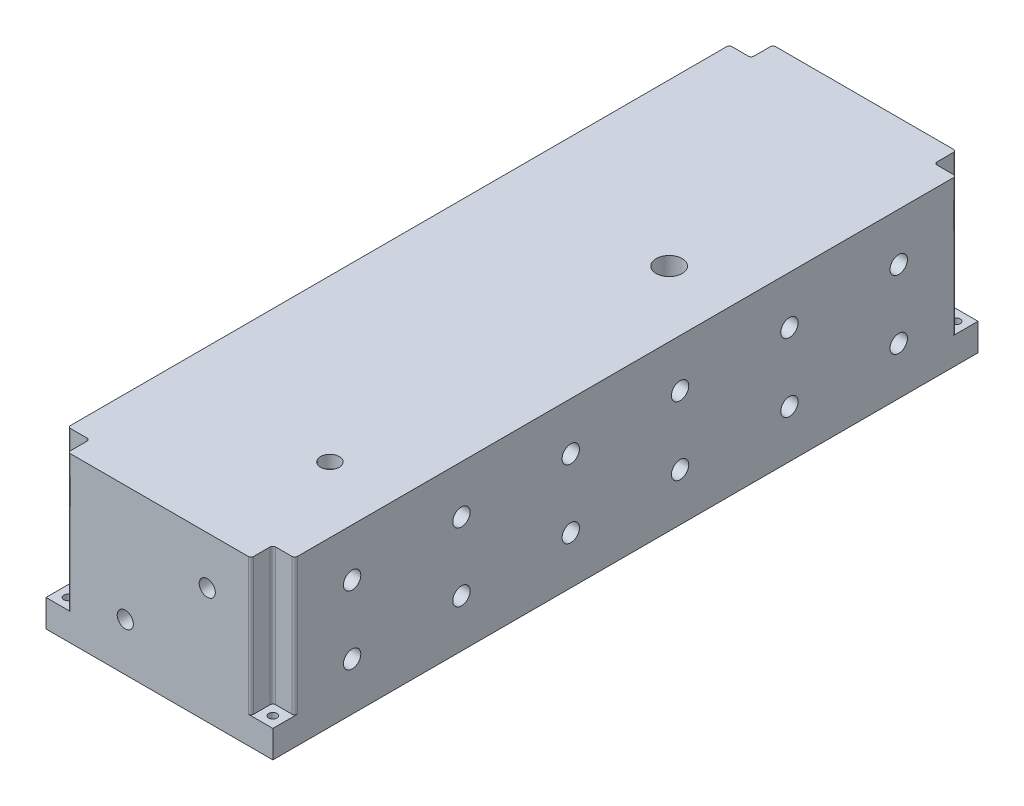
SolidWorks part; units mm, degrees
material "Liga 6061"
ref_plane "Plano frontal" through (0, 0, 0) normal (0, 0, 1) x (1, 0, 0)
ref_plane "Plano superior" through (0, 0, 0) normal (0, 1, 0) x (1, 0, 0)
ref_plane "Plano direito" through (0, 0, 0) normal (1, 0, 0) x (0, 0, -1)
sketch "Esboço1" plane through (0, 0, 0) normal (0, 0, 1) x (1, 0, 0)
  line L0 (83, 0) -> (83, 120) construction
  line L1 (0, 120) -> (166, 120)
  line L2 (0, 120) -> (0, 0)
  line L3 (0, 0) -> (166, 0)
  line L4 (166, 120) -> (166, 0)
  circle A0 centre (118, 85) radius 9.525 construction
  circle A1 centre (58, 35) radius 9.525 construction
  circle A2 centre (118, 85) radius 24 construction
  circle A3 centre (58, 35) radius 24 construction
  dimension "D4" = 19.05
  dimension "D5" = 19.05
  dimension "D6" = 50
  dimension "D7" = 35
  dimension "D8" = 25
  dimension "D3" = 35
  dimension "D1" = 166
  dimension "D2" = 120
extrude "Ressalto-extrusão2" add sketch "Esboço1" along normal blind 516
sketch "Esboço19" plane through (0, 0, 0) normal (0, 0, -1) x (-1, 0, 0)
  circle A1 centre (-118, 85) radius 9.525 construction
  circle A2 centre (-118, 85) radius 9.525
extrude "FuroLinhaP" cut sketch "Esboço19" against normal offset from surface (490.6 mm away) 25.4 up to face at (83, 60, 516)
sketch "Esboço21" plane through (0, 0, 0) normal (0, 0, -1) x (-1, 0, 0)
  circle A1 centre (-58, 35) radius 9.525 construction
  circle A2 centre (-58, 35) radius 9.525
extrude "FuroLinhaT" cut sketch "Esboço21" against normal offset from surface (490.6 mm away) 25.4 up to face at (83, 60, 516)
ref_axis "EixoP" through (118, 85, 490.6) along (0, 0, -1)
ref_axis "EixoT" through (58, 35, 490.6) along (0, 0, -1)
sketch "Esboço3" plane through (0, 0, 0) normal (0, 0, -1) x (-1, 0, 0)
  text T0 "P"
  dimension "D1" = 30.4313
extrude "LetraP" add sketch "Esboço3" along normal blind 0.5
sketch "Esboço4" plane through (0, 0, 0) normal (0, 0, -1) x (-1, 0, 0)
  text T0 "T"
  dimension "D1" = 19.8213
extrude "LetraT" cut sketch "Esboço4" against normal blind 0.5
sketch "Esboço12" plane through (0, 120, 0) normal (0, 1, 0) x (1, 0, 0)
  line L1 (166, 0) -> (150, 0)
  line L2 (166, 0) -> (166, -16)
  line L3 (166, -16) -> (150, -16)
  line L4 (150, 0) -> (150, -16)
  line L5 (0, -258) -> (166, -258) construction
  line L6 (0, -516) -> (0, 0) construction
  line L7 (166, -516) -> (166, 0) construction
  line L10 (166, 0) -> (0, 0) construction
  line L11 (83, -516) -> (83, 0) construction
  line L12 (166, -516) -> (0, -516) construction
  line L13 (16, 0) -> (16, -16)
  line L14 (0, -16) -> (16, -16)
  line L15 (0, 0) -> (0, -16)
  line L16 (0, 0) -> (16, 0)
  line L17 (0, -516) -> (16, -516)
  line L18 (0, -516) -> (0, -500)
  line L19 (0, -500) -> (16, -500)
  line L20 (16, -516) -> (16, -500)
  line L21 (150, -516) -> (150, -500)
  line L22 (166, -500) -> (150, -500)
  line L23 (166, -516) -> (166, -500)
  line L24 (166, -516) -> (150, -516)
  circle A0 centre (120.5, -8) radius 3 construction
  circle A1 centre (120.5, -8) radius 5.775 construction
  dimension "D6" = 6
  dimension "D7" = 11.55
  dimension "D1" = 16
  dimension "D2" = 16
  dimension "D3" = 258
  dimension "D4" = 37.5
  dimension "D5" = 8
extrude "Corte-extrusão5" cut sketch "Esboço12" against normal offset from surface (100 mm away) 20 up to face at (83, 0, 258)
hole_wizard "Furos-guia com Ø6.0mm1" positions "Esboço13" profile "Esboço14" hole size "Ø6.0" standard "ISO" end condition through all
sketch "Esboço13" plane through (0, 20, 0) normal (0, 1, 0) x (1, 0, 0)
  line L1 (166, 0) -> (150, 0) construction
  line L2 (150, 0) -> (16, 0) construction
  point P0 (158, -8)
  point P9 (83, 0)
  dimension "D1" = 75
  dimension "D2" = 8
sketch "Esboço14" plane through (158, 20, 8) normal (1, 0, 0) x (0, 0, 1)
  line L0 (0, 0) -> (0, 20)
  line L1 (0, 20) -> (3, 20)
  line L2 (3, 20) -> (3, 0)
  line L5 (3, 0) -> (0, 0)
  line L11 (0, -6.35) -> (0, 107.95) construction
  dimension "Thru Hole Dia." = 6
  dimension "Thru Hole Depth" = 20
ref_plane "Plano2" through (83, 0, 0) normal (1, 0, 0) x (0, 0, -1)
ref_plane "Plano3" through (0, 0, 258) normal (0, 0, 1) x (1, 0, 0)
mirror "Espelhar1" about plane through (0, 0, 258) normal (0, 0, 1) of "Furos-guia com Ø6.0mm1"
mirror "Espelhar2" about plane through (83, 0, 0) normal (1, 0, 0) of "Espelhar1"
fillet "Filete2" radius 2 3 edges at (150, 70, 16) (166, 70, 16) (150, 70, 0)
fillet "Filete3" radius 2 3 edges at (16, 70, 16) (16, 70, 0) (0, 70, 16)
fillet "Filete4" radius 2 3 edges at (166, 70, 500) (150, 70, 500) (150, 70, 516)
fillet "Filete5" radius 2 3 edges at (16, 70, 516) (16, 70, 500) (0, 70, 500)
hole_wizard "Furo roscado de G1/4 SensorP BSP" positions "Esboço43" profile "Esboço44" tap size "G1/4" standard "BSI" end condition through all
sketch "Esboço43" plane through (0, 0, 516) normal (0, 0, 1) x (1, 0, 0)
  point P6 (118, 85)
sketch "Esboço44" plane through (118, 85, 516) normal (1, 0, 0) x (0, -1, 0)
  line L0 (0, 0) -> (0, 516.5)
  line L1 (0, 516.5) -> (5.9, 516.5)
  line L2 (5.9, 516.5) -> (5.9, 0)
  line L5 (5.9, 0) -> (0, 0)
  line L11 (0, -6.35) -> (0, 107.95) construction
  dimension "Thru Tap Drill Dia." = 11.8
  dimension "Thru Tap Drill Depth" = 516.5
cosmetic thread "Rosca de furo2" parameters "D1"=11, "D2"=13.157
hole_wizard "Furo roscado de G1/4 SensorT BSP" positions "Esboço45" profile "Esboço46" tap size "G1/4" standard "BSI" end condition through all
sketch "Esboço45" plane through (0, 0, 516) normal (0, 0, 1) x (1, 0, 0)
  point P3 (58, 35)
sketch "Esboço46" plane through (58, 35, 516) normal (1, 0, 0) x (0, -1, 0)
  line L0 (0, 0) -> (0, 516.5)
  line L1 (0, 516.5) -> (5.9, 516.5)
  line L2 (5.9, 516.5) -> (5.9, 0)
  line L5 (5.9, 0) -> (0, 0)
  line L11 (0, -6.35) -> (0, 107.95) construction
  dimension "Thru Tap Drill Dia." = 11.8
  dimension "Thru Tap Drill Depth" = 516.5
cosmetic thread "Rosca de furo3" parameters "D1"=11, "D2"=13.157
sketch "Esboço51" plane through (166, 0, 0) normal (1, 0, 0) x (0, 0, -1)
  line L0 (-258, 120) -> (-258, 0) construction
  line L1 (-498, 120) -> (-18, 120) construction
  line L2 (-516, 0) -> (0, 0) construction
  line L3 (-490.6, 85) -> (0, 85) construction
  circle A0 centre (-218, 85) radius 6.35
  circle A1 centre (-218, 85) radius 19 construction
  circle A3 centre (-138, 85) radius 6.35
  circle A4 centre (-138, 85) radius 19 construction
  circle A5 centre (-58, 85) radius 6.35
  circle A6 centre (-58, 85) radius 19 construction
  circle A7 centre (-458, 85) radius 19 construction
  circle A8 centre (-378, 85) radius 19 construction
  circle A9 centre (-298, 85) radius 19 construction
  circle A10 centre (-458, 85) radius 6.35
  circle A11 centre (-378, 85) radius 6.35
  circle A12 centre (-298, 85) radius 6.35
  dimension "D1" = 3
  dimension "D2" = 40
extrude "Corte-extrusão Distribuição P" cut sketch "Esboço51" against normal up to next
sketch "Esboço52" plane through (166, 0, 0) normal (1, 0, 0) x (0, 0, -1)
  line L0 (-258, 120) -> (-258, 0) construction
  line L1 (-498, 120) -> (-18, 120) construction
  line L2 (-516, 0) -> (0, 0) construction
  line L3 (-490.6, 35) -> (0, 35) construction
  circle A0 centre (-218, 35) radius 6.35
  circle A1 centre (-218, 35) radius 19 construction
  circle A2 centre (-138, 35) radius 6.35
  circle A3 centre (-138, 35) radius 19 construction
  circle A4 centre (-58, 35) radius 6.35
  circle A5 centre (-58, 35) radius 19 construction
  circle A6 centre (-458, 35) radius 19 construction
  circle A7 centre (-378, 35) radius 19 construction
  circle A8 centre (-298, 35) radius 19 construction
  circle A9 centre (-458, 35) radius 6.35
  circle A10 centre (-378, 35) radius 6.35
  circle A11 centre (-298, 35) radius 6.35
  dimension "D1" = 12.7
  dimension "D3" = 3
  dimension "D2" = 40
extrude "Corte-extrusão Distribuição T" cut sketch "Esboço52" against normal up to next
hole_wizard "Furo roscado de G1/4 Barometro NPT" positions "Esboço47" profile "Esboço48" size "1/4" standard "Ansi Inch" end condition up to next
sketch "Esboço47" plane through (0, 120, 0) normal (0, 1, 0) x (1, 0, 0)
  line L0 (148, -516) -> (18, -516) construction
  line L1 (83, -516) -> (83, 0) construction
  line L2 (148, 0) -> (18, 0) construction
  line L3 (118, -490.6) -> (118, 0) construction
  line L4 (94.0012, -426.25) -> (151.1512, -426.25) construction
  line L6 (166, -451.65) -> (127.525, -451.65) construction
  point P0 (118, -426.25)
  dimension "D1" = 25.4
  dimension "D2" = 89.75
sketch "Esboço48" plane through (118, 120, 426.25) normal (1, 0, 0) x (0, 0, 1)
  line L0 (0, 0) -> (0, 25.475)
  line L1 (0, 25.475) -> (5.5626, 25.475)
  line L2 (-6.558, 9) -> (-6.8275, 0) construction
  line L3 (5.5626, 25.475) -> (5.5626, 9)
  line L4 (5.5626, 9) -> (6.558, 9)
  line L5 (6.558, 9) -> (6.8275, 0)
  line L7 (6.8275, 0) -> (0, 0)
  line L8 (0, -6.35) -> (0, 107.95) construction
  line L11 (-5.5626, 9) -> (-6.558, 9) construction
  dimension "Thru Tap Drill Dia." = 11.1252
  dimension "Thru Tap Drill Depth" = 25.475
  dimension "Thread Dia." = 13.6549
  dimension "Thread Angle" = 3.43
  dimension "Thread Depth" = 9
hole_wizard "Furo roscado de G1/2 Acumulador BSP" positions "Esboço49" profile "Esboço50" tap size "G1/2" standard "BSI" end condition up to next
sketch "Esboço49" plane through (0, 120, 0) normal (0, 1, 0) x (1, 0, 0)
  line L0 (148, 0) -> (18, 0) construction
  line L1 (83, -516) -> (83, 0) construction
  line L2 (148, -516) -> (18, -516) construction
  line L3 (118, -490.6) -> (118, 0) construction
  line L4 (155.5279, -178) -> (73.6801, -178) construction
  line L6 (67.525, -144.35) -> (166, -144.35) construction
  line L7 (166, -211.65) -> (67.525, -211.65) construction
  line L8 (67.525, -144.35) -> (166, -144.35) construction
  point P0 (118, -178)
  dimension "D2" = 33.65
cosmetic thread "Rosca de furo5" parameters "D1"=25, "D2"=20.955
sketch "Esboço50" plane through (118, 120, 178) normal (1, 0, 0) x (0, 0, 1)
  line L0 (0, 0) -> (0, 25.475)
  line L1 (0, 25.475) -> (9.5, 25.475)
  line L2 (9.5, 25.475) -> (9.5, 0)
  line L5 (9.5, 0) -> (0, 0)
  line L11 (0, -6.35) -> (0, 107.95) construction
  dimension "Thru Tap Drill Dia." = 19
  dimension "Thru Tap Drill Depth" = 25.475
